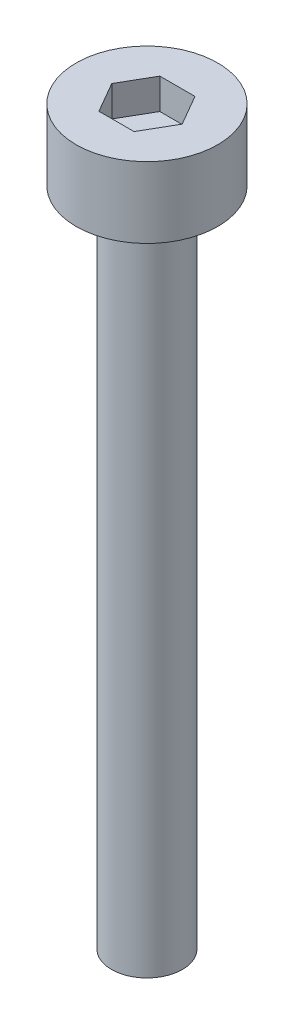
SolidWorks part; units mm, degrees
ref_plane "Front Plane" through (0, 0, 0) normal (0, 0, 1) x (1, 0, 0)
ref_plane "Top Plane" through (0, 0, 0) normal (0, 1, 0) x (1, 0, 0)
ref_plane "Right Plane" through (0, 0, 0) normal (1, 0, 0) x (0, 0, -1)
sketch "Sketch1" plane through (0, 0, 0) normal (0, 1, 0) x (1, 0, 0)
  circle A0 centre (0, 0) radius 1.5
  dimension "D1" = 3
extrude "ScrewShaft" add sketch "Sketch1" along normal blind 28
sketch "Sketch2" plane through (0, 28, 0) normal (0, 1, 0) x (1, 0, 0)
  circle A0 centre (0, 0) radius 3
  dimension "D1" = 6
extrude "Boss-Extrude2" add sketch "Sketch2" along normal blind 3
sketch "Sketch3" plane through (0, 31, 0) normal (0, 1, 0) x (1, 0, 0)
  line L0 (0, 0) -> (0, 1.29) construction
  line L1 (1.4896, 0) -> (0.7448, 1.29)
  line L2 (0.7448, 1.29) -> (-0.7448, 1.29)
  line L3 (-0.7448, 1.29) -> (-1.4896, 0)
  line L4 (-1.4896, 0) -> (-0.7448, -1.29)
  line L5 (-0.7448, -1.29) -> (0.7448, -1.29)
  line L6 (0.7448, -1.29) -> (1.4896, 0)
  circle A0 centre (0, 0) radius 1.29 construction
  dimension "D1" = 2.58
extrude "Cut-Extrude1" cut sketch "Sketch3" against normal blind 1.3
equation "\"X-ROD-SPACING\"=45"
equation "\"Y-ROD-SPACING\"=75"
equation "\"Z-ROD-SPACING\"=17.5"
equation "\"Y-BED-OFFSET\"=2"
equation "\"Y-BED-ROD-INSET\"=3.5"
equation "\"T-SLOT-NUT-FILLET-RADIUS\"=0.5"
equation "\"T-SLOT-SCREW-SHAFT-RADIUS\"=1.55"
equation "\"T-SLOT-SCREW-SHAFT-CUTOUT-LENGTH\"=11"
equation "\"T-SLOT-NUT-DEPTH\"=3.5"
equation "\"T-SLOT-NUT-WIDTH\"=2.85"
equation "\"T-SLOT-NUT-END-DISTANCE\"=8"
equation "\"ACRYLIC-THICKNESS\"=10"
equation "\"ACRYLIC-THICKNESS2\"=4.5"
equation "\"ACRYLIC-TAB-CUTOUT-SIZE\"=\"ACRYLIC-THICKNESS\"+\"ACRYLIC-TAB-TOLERANCE\"*2"
equation "\"ACRYLIC-TAB-WIDTH\"=\"ACRYLIC-THICKNESS\""
equation "\"ACRYLIC-M3-HOLE\"=2.9"
equation "\"SMOOTHROD-CAP-SCREW-DISTANCE\"=20"
equation "\"FRAME-WIDTH-INNER\"=370"
equation "\"NEMA17-HOLE-SPACING\"=31"
equation "\"NEMA17-CENTRAL-CUTOUT\"=22.5"
equation "\"Z-BRACKET-REACH\"=57"
equation "\"TOP-BRACKET-SPACING\"=40"
equation "\"SMOOTHROD-X-LENGTH\"=350"
equation "\"SMOOTHROD-Y-LENGTH\"=350"
equation "\"SMOOTHROD-Z-LENGTH\"=350"
equation "\"SMOOTHROD-TIGHTENING-HEADROOM\"=.25"
equation "\"LEADSCREW-Z-LENGTH\"=300"
equation "\"SCREW-LENGTH-FRAME\"=\"ACRYLIC-THICKNESS\" + 10"
equation "\"SCREW-HEAD-RADIUS\"=6"
equation "\"PRINTED-X-SMOOTHROD-DIAMETER\"=8.8"
equation "\"PRINTED-X-SMOOTHROD-CUTOUT\"=10"
equation "\"PRINTED-X-BASE-HEIGHT\"=10"
equation "\"PRINTED-LM8UU-CUTOUT-SIZE\"=15.5"
equation "\"PRINTED-LM8UU-CUTOUT-LENGTH\"=24.5"
equation "\"PRINTED-X-IDLER-HEIGHT\"=16"
equation "\"PSU-MOUNTING-WIDTH\"=95"
equation "\"PSU-MOUNTING-HEIGHT\"=177"
equation "\"D1@ScrewShaft\"=\"SCREW-LENGTH-EXTRUDER\""
equation "\"D1@Sketch2\"=\"SCREW-HEAD-RADIUS\""
equation "\"Y-BED-SCREW-SPACING\"=209"
equation "\"Y-BED-SCREW-CUTOUT-SLOT-HEIGHT\"=2.5"
equation "\"Z-ROD-INSET\"=13.5"
equation "\"SCREW-LENGTH-MOTOR\"=\"ACRYLIC-THICKNESS\" + 5"
equation "\"SCREW-LENGTH-EXTRUDER\"=28"
equation "\"Y-BELT-TO-ROD-DISTANCE\"=20"
equation "\"SPOOL-HOLDER-ROD-SPACING\"=150"
equation "\"ACRYLIC-X-CARRIAGE-WIDTH\"=55"
equation "\"ACRYLIC-X-CARRIAGE-HEIGHT\"=75"
equation "\"ACRYLIC-X-CARRIAGE-CENTER-TAB-SPACING\"=14"
